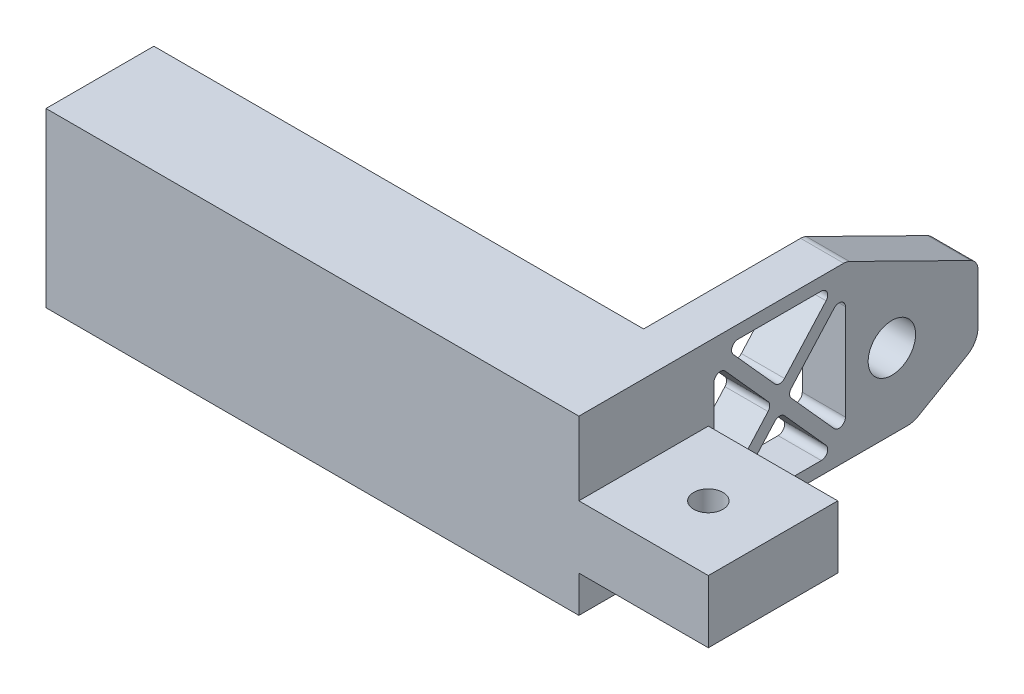
SolidWorks part; units mm, degrees
material "PLA"
ref_plane "Front Plane" through (0, 0, 0) normal (0, 0, 1) x (1, 0, 0)
ref_plane "Top Plane" through (0, 0, 0) normal (0, 1, 0) x (1, 0, 0)
ref_plane "Right Plane" through (0, 0, 0) normal (1, 0, 0) x (0, 0, -1)
sketch "Sketch1" plane through (0, 0, 0) normal (1, 0, 0) x (0, 0, -1)
  line L1 (-35.9146, 20.1296) -> (56.5854, 20.1296)
  line L2 (-35.9146, 20.1296) -> (-35.9146, -19.8704)
  line L3 (-35.9146, -19.8704) -> (56.5854, -19.8704)
  line L4 (56.5854, 20.1296) -> (56.5854, -19.8704)
  dimension "D1" = 92.5
  dimension "D2" = 40
extrude "Boss-Extrude1" add sketch "Sketch1" along normal blind 10
sketch "Sketch4" plane through (0, 0, 0) normal (-1, 0, 0) x (0, 0, 1)
  line L11 (-56.5854, 20.1296) -> (35.9146, 20.1296) construction
  line L12 (10.9146, 20.1296) -> (35.9146, 20.1296)
  line L13 (10.9146, 20.1296) -> (10.9146, -19.8704)
  line L14 (10.9146, -19.8704) -> (35.9146, -19.8704)
  line L15 (35.9146, 20.1296) -> (35.9146, -19.8704)
  line L16 (10.9146, 20.1296) -> (35.9146, -19.8704) construction
  line L17 (10.9146, -19.8704) -> (35.9146, 20.1296) construction
  line L18 (18.4146, 12.6296) -> (18.4146, -12.3704)
  line L19 (18.4146, -12.3704) -> (28.4146, -12.3704)
  line L20 (28.4146, 12.6296) -> (28.4146, -12.3704)
  line L21 (18.4146, 12.6296) -> (28.4146, 12.6296)
  point P4 (23.4146, 0.1296)
  dimension "D1" = 25
  dimension "D2" = 7.5
sketch "Sketch5" plane through (0, 0, 0) normal (-1, 0, 0) x (0, 0, 1)
  line L0 (35.9146, -19.8704) -> (-56.5854, -19.8704) construction
  line L2 (35.9146, 20.1296) -> (35.9146, -19.8704) construction
  circle A0 centre (-36.6254, -2.4304) radius 5.5
  dimension "D1" = 11
  dimension "D2" = 17.44
  dimension "D3" = 72.54
extrude "Cut-Extrude1" cut sketch "Sketch5" against normal blind 27
sketch "Sketch6" plane through (10, 0, 0) normal (1, 0, 0) x (0, 0, -1)
  line L0 (-35.9146, 20.1296) -> (-35.9146, -19.8704) construction
  line L1 (-5.9146, -2.8704) -> (-35.9146, -2.8704)
  line L2 (-5.9146, -2.8704) -> (-5.9146, 3.1296)
  line L3 (-5.9146, 3.1296) -> (-35.9146, 3.1296)
  line L4 (-35.9146, -2.8704) -> (-35.9146, 3.1296)
  line L5 (-5.9146, -2.8704) -> (-35.9146, 3.1296) construction
  line L6 (-5.9146, 3.1296) -> (-35.9146, -2.8704) construction
  line L8 (-35.9146, -19.8704) -> (56.5854, -19.8704) construction
  point P0 (-20.9146, 0.1296)
  dimension "D1" = 30
  dimension "D2" = 6
  dimension "D3" = 20
extrude "Boss-Extrude5" add sketch "Sketch6" along normal blind 30
sketch "Sketch7" plane through (0, -2.8704, 0) normal (0, -1, 0) x (1, 0, 0)
  line L1 (40, 35.9146) -> (10, 35.9146)
  line L2 (40, 35.9146) -> (40, 5.9146)
  line L3 (40, 5.9146) -> (10, 5.9146)
  line L4 (10, 35.9146) -> (10, 5.9146)
extrude "Boss-Extrude6" add sketch "Sketch7" along normal blind 8.5
extrude "Boss-Extrude7" add sketch "Sketch4" along normal blind 113.5
fillet "Fillet1" radius 3 4 edges at (-113.5, -12.3704, 23.4146) (-113.5, 0.1296, 28.4146) (-113.5, 12.6296, 23.4146) (-113.5, 0.1296, 18.4146)
chamfer "Chamfer1" distance 15 angle 63.75 1 edges at (5, 20.1296, -56.5854) first distance on face at (5, 0.1296, -56.5854)
fillet "Fillet3" radius 3 2 edges at (5, 20.1296, -26.1684) (5, 5.1296, -56.5854)
chamfer "Chamfer3" distance 15 angle 30 1 edges at (5, -19.8704, -56.5854) first distance on face at (-34.5, -19.8704, -3.252)
fillet "Fillet7" radius 5 2 edges at (5, -19.8704, -41.5854) (5, -11.2102, -56.5854)
sketch "Sketch9" plane through (10, 0, 0) normal (1, 0, 0) x (0, 0, -1)
  line L6 (25.8575, 15.1296) -> (12.4139, 0.1296)
  line L7 (12.4139, 0.1296) -> (25.8575, -14.8704)
  line L8 (25.8575, -14.8704) -> (25.8575, 0.1296)
  line L9 (25.4689, 20.1296) -> (-35.9146, 20.1296) construction
  line L10 (-4.6146, 17.1296) -> (25.8575, 17.1296)
  line L11 (-4.6146, 17.1296) -> (-4.6146, -16.8704)
  line L12 (-4.6146, -16.8704) -> (25.8575, -16.8704)
  line L13 (25.8575, 17.1296) -> (25.8575, -16.8704)
  line L14 (-35.9146, -19.8704) -> (40.2456, -19.8704) construction
  line L15 (-4.6146, 17.1296) -> (25.8575, -16.8704) construction
  line L16 (25.8575, 17.1296) -> (-4.6146, -16.8704) construction
  line L17 (-4.6146, 0.1296) -> (25.8575, 0.1296) construction
  line L18 (10.6214, 17.1296) -> (10.6214, -16.8704) construction
  line L19 (10.6214, 17.1296) -> (23.6214, 17.1296)
  line L20 (23.6214, 17.1296) -> (10.6214, 2.6245)
  line L21 (10.6214, 2.6245) -> (-2.3786, 17.1296)
  line L22 (-2.3786, 17.1296) -> (10.6214, 17.1296)
  line L23 (-2.3786, 17.1296) -> (23.6214, 17.1296)
  line L24 (25.8575, 0.1296) -> (25.8575, 15.1296)
  line L25 (-5.9146, -11.3704) -> (-5.9146, 3.1296) construction
  line L26 (10.6214, -2.3654) -> (-2.3786, -16.8704)
  line L27 (23.6214, -16.8704) -> (10.6214, -2.3654)
  line L28 (10.6214, -16.8704) -> (23.6214, -16.8704)
  line L29 (-2.3786, -16.8704) -> (10.6214, -16.8704)
  line L30 (-4.6146, -14.8704) -> (-4.6146, 0.1296)
  line L31 (8.829, 0.1296) -> (-4.6146, -14.8704)
  line L32 (-4.6146, 15.1296) -> (8.829, 0.1296)
  line L33 (-4.6146, 0.1296) -> (-4.6146, 15.1296)
  dimension "D1" = 3
  dimension "D2" = 3
  dimension "D3" = 13
  dimension "D4" = 13
  dimension "D5" = 3
  dimension "D6" = 15
  dimension "D7" = 15
  dimension "D8" = 1.3
sketch "Sketch10" plane through (0, 3.1296, 0) normal (0, 1, 0) x (1, 0, 0)
  line L0 (40, -5.9146) -> (10, -35.9146) construction
  line L1 (40, -35.9146) -> (10, -5.9146) construction
  point P10 (25, -20.9146)
hole_wizard "M8 Tapped Hole1" positions "Sketch10" profile "Sketch11" tap size "M8" standard "ISO"
sketch "Sketch11" plane through (25, 3.1296, 20.9146) normal (1, 0, 0) x (0, 0, 1)
  line L0 (0, 0) -> (0, 24.2929)
  line L1 (0, 24.2929) -> (3.4, 22.25)
  line L2 (3.4, 22.25) -> (3.4, 0)
  line L5 (3.4, 0) -> (0, 0)
  line L10 (0, 24.2929) -> (-3.4, 22.25) construction
  line L11 (0, -6.35) -> (0, 107.95) construction
  dimension "Tap Drill Dia." = 6.8
  dimension "Tap Drill Depth" = 22.25
  dimension "Drill Angle" = 118
cosmetic thread "Hole Thread1" parameters "D1"=16, "D2"=8
extrude "Cut-Extrude2" cut sketch "Sketch9" against normal through all contours L22 L19 L20 L21 | L24 L6 L7 L8 | L26 L29 L28 L27 | L30 L33 L32 L31
fillet "Fillet8" radius 1.5 12 edges at (5, -14.8704, 4.6146) (5, 15.1296, 4.6146) (5, 0.1296, -8.829) (5, -16.8704, 2.3786) (5, -16.8704, -23.6214) (5, -2.3654, -10.6214) (5, -14.8704, -25.8575) (5, 0.1296, -12.4139) (5, 15.1296, -25.8575) (5, 2.6245, -10.6214) (5, 17.1296, -23.6214) (5, 17.1296, 2.3786)
